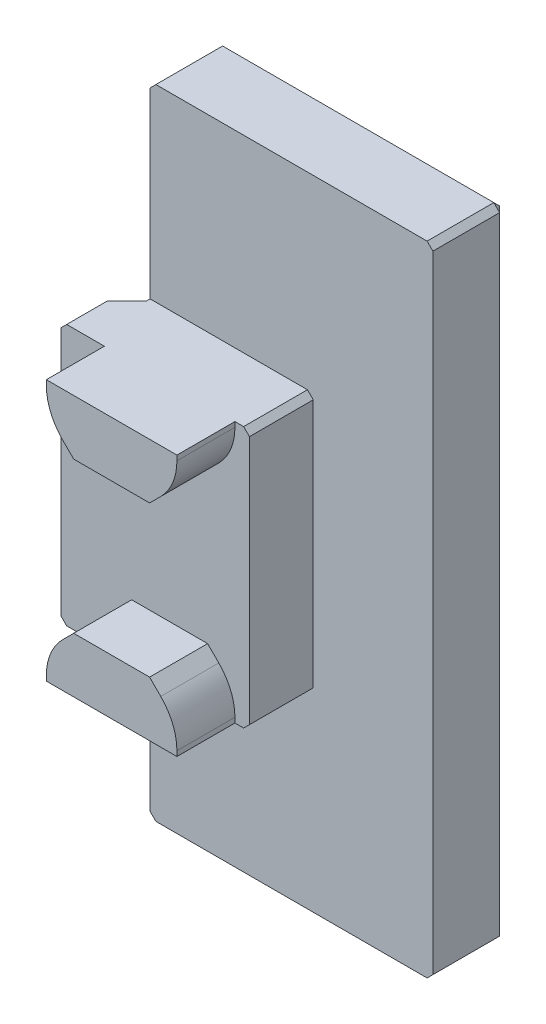
SolidWorks part; units mm, degrees
ref_plane "Front" through (0, 0, 0) normal (0, 0, 1) x (1, 0, 0)
ref_plane "Top" through (0, 0, 0) normal (0, 1, 0) x (1, 0, 0)
ref_plane "Right" through (0, 0, 0) normal (1, 0, 0) x (0, 0, -1)
sketch "Sketch1" plane through (0, 0, 0) normal (0, 0, 1) x (1, 0, 0)
  line L0 (-2.75, -11.5) -> (-2.75, -5) construction
  line L1 (2.75, -4.5) -> (-2.75, -4.5)
  line L2 (2.75, -4.5) -> (2.75, 4.5)
  line L3 (2.75, 4.5) -> (-2.75, 4.5)
  line L4 (-2.75, -4.5) -> (-2.75, 4.5) construction
  line L5 (2.75, -4.5) -> (-2.75, 4.5) construction
  line L6 (2.75, 4.5) -> (-2.75, -4.5) construction
  line L7 (-2.35, -4.5) -> (-3.75, -4.5) construction
  line L8 (-2.75, 4.5) -> (-3.75, 4.5)
  line L9 (-3.75, 4.5) -> (-3.75, -4.5)
  line L10 (-3.75, -4.5) -> (-2.75, -4.5)
  point P0 (0, 0)
extrude "Boss-Extrude1" add sketch "Sketch1" against normal blind 2
sketch "Sketch2" plane through (0, 0, 0) normal (0, 0, 1) x (1, 0, 0)
  line L0 (-2.25, -4.3284) -> (-2.25, -4.5)
  line L1 (-1.6935, -6.5151) -> (-1.3086, -6.9) construction
  line L2 (-1.3086, -6.9) -> (1.3086, -6.9) construction
  line L3 (1.3086, -6.9) -> (1.6935, -6.5151) construction
  line L4 (2.25, -5.1716) -> (2.25, -4.3284) construction
  line L5 (1.6935, -2.9849) -> (1.3086, -2.6)
  line L6 (1.3086, -2.6) -> (-1.3086, -2.6)
  line L7 (-1.3086, -2.6) -> (-1.6935, -2.9849)
  line L8 (-2.25, -4.3284) -> (-2.25, -5.1716) construction
  line L9 (1.35, -7) -> (1.7642, -6.5858)
  line L10 (-1.35, -7) -> (1.35, -7)
  line L11 (-1.7642, -6.5858) -> (-1.35, -7)
  line L12 (-2.35, -4.3284) -> (-2.35, -5.1716)
  line L13 (-1.35, -2.5) -> (-1.7642, -2.9142)
  line L14 (1.35, -2.5) -> (-1.35, -2.5)
  line L15 (1.7642, -2.9142) -> (1.35, -2.5)
  line L16 (2.35, -5.1716) -> (2.35, -4.3284)
  line L17 (1.35, -7) -> (1.7642, -6.5858) construction
  line L18 (-1.35, -7) -> (1.35, -7) construction
  line L20 (-1.7642, -6.5858) -> (-1.35, -7) construction
  line L22 (-2.35, -4.3284) -> (-2.35, -5.1716) construction
  line L24 (-1.35, -2.5) -> (-1.7642, -2.9142) construction
  line L26 (1.35, -2.5) -> (-1.35, -2.5) construction
  line L28 (1.7642, -2.9142) -> (1.35, -2.5) construction
  line L30 (2.35, -5.1716) -> (2.35, -4.3284) construction
  line L32 (2.25, -4.3284) -> (2.25, -4.5)
  line L39 (-2.75, -4.5) -> (2.75, -4.5)
  line L40 (-3.75, -4.5) -> (-2.75, -4.5)
  line L41 (-3.75, 4.5) -> (-3.75, -4.5)
  line L46 (-2.75, 4.5) -> (-3.75, 4.5)
  line L48 (2.75, 4.5) -> (-2.75, 4.5)
  line L54 (2.75, -4.5) -> (2.75, 4.5)
  line L58 (-2.25, -4.5) -> (2.25, -4.5)
  arc A0 (-2.25, -5.1716) -> (-1.6935, -6.5151) centre (-0.35, -5.1716) ccw construction
  arc A2 (1.6935, -6.5151) -> (2.25, -5.1716) centre (0.35, -5.1716) ccw construction
  arc A4 (2.25, -4.3284) -> (1.6935, -2.9849) centre (0.35, -4.3284) ccw
  arc A5 (-1.6935, -2.9849) -> (-2.25, -4.3284) centre (-0.35, -4.3284) ccw
  arc A7 (-2.35, -5.1716) -> (-1.7642, -6.5858) centre (-0.35, -5.1716) ccw
  arc A8 (-1.7642, -2.9142) -> (-2.35, -4.3284) centre (-0.35, -4.3284) ccw
  arc A10 (2.35, -4.3284) -> (1.7642, -2.9142) centre (0.35, -4.3284) ccw
  arc A11 (1.7642, -6.5858) -> (2.35, -5.1716) centre (0.35, -5.1716) ccw
  arc A12 (-2.35, -5.1716) -> (-1.7642, -6.5858) centre (-0.35, -5.1716) ccw construction
  arc A13 (-1.7642, -2.9142) -> (-2.35, -4.3284) centre (-0.35, -4.3284) ccw construction
  arc A14 (2.35, -4.3284) -> (1.7642, -2.9142) centre (0.35, -4.3284) ccw construction
  arc A15 (1.7642, -6.5858) -> (2.35, -5.1716) centre (0.35, -5.1716) ccw construction
  dimension "D1" = 0
  dimension "D2" = 0.1
  dimension "D3" = 0
extrude "Slot Tab" add sketch "Sketch2" along normal blind 2 contours L7 A5 L0 L58 L32 A4 L5 L6 region at (0, -3.6243, 0)
mirror "Slot Tabs" about plane through (0, 0, 0) normal (0, 1, 0) of "Slot Tab"
chamfer "Deburs" [suppressed] distance 0.2 angle 45
sketch "Sketch3" plane through (0, 0, -2) normal (0, 0, -1) x (-1, 0, 0)
  line L4 (3.75, 4.5) -> (-2.75, 4.5)
  line L5 (-2.75, 4.5) -> (-2.75, -4.5)
  line L6 (-2.75, -4.5) -> (3.75, -4.5)
  line L7 (3.75, -4.5) -> (3.75, 4.5)
  line L8 (3.75, 4.5) -> (-2.75, 4.5)
  line L9 (-2.75, 4.5) -> (-2.75, -4.5)
  line L10 (-2.75, -4.5) -> (3.75, -4.5)
  line L11 (3.75, -4.5) -> (3.75, 4.5)
  dimension "D1" = 0
extrude "Stopper Clearance" add sketch "Sketch3" along normal blind 0.2
sketch "Sketch4" plane through (0, 0, -2.2) normal (0, 0, -1) x (-1, 0, 0)
  line L1 (2.875, -11) -> (-6.875, -11)
  line L2 (2.875, -11) -> (2.875, 11)
  line L3 (2.875, 11) -> (-6.875, 11)
  line L4 (-6.875, -11) -> (-6.875, 11)
  line L5 (2.875, -11) -> (-6.875, 11) construction
  line L6 (2.875, 11) -> (-6.875, -11) construction
  point P0 (-2, 0)
  dimension "D1" = 2
  dimension "D2" = 22
  dimension "D3" = 9.75
extrude "Stopper" add sketch "Sketch4" along normal blind 2.5
chamfer "Deburs 2" distance 0.2 angle 45 12 edges at (2.75, 4.5, -1.1) (2.75, -4.5, -1.1) (-3.75, -4.5, -1.1) (-3.75, 4.5, -1.1) (2, 11, -4.7) (-2.875, 11, -3.45) (-2.875, 0, -4.7) (6.875, 11, -3.45) (6.875, 0, -4.7) (6.875, -11, -3.45) (2, -11, -4.7) (-2.875, -11, -3.45)
chamfer "Chamfer3" distance 1 angle 45 1 edges at (-3.75, 0, -2.2)
